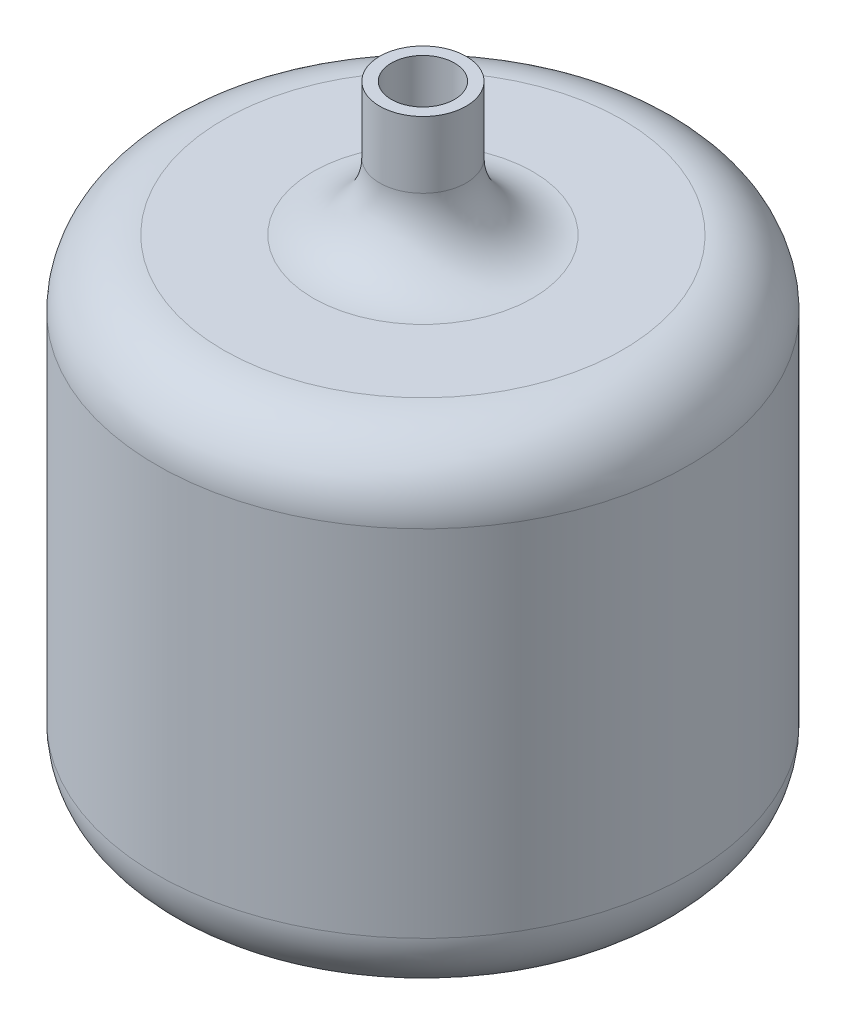
SolidWorks part; units mm, degrees
ref_plane "Plan de face" through (0, 0, 0) normal (1, 0, 0) x (0, 1, 0)
ref_plane "Plan de dessus" through (0, 0, 0) normal (0, 0, 1) x (0, 1, 0)
ref_plane "Plan de droite" through (0, 0, 0) normal (0, 1, 0) x (-1, 0, 0)
sketch "Esquisse1" plane through (0, 0, 0) normal (0, 0, 1) x (0, 1, 0)
  line L0 (0, 0) -> (64.4456, 0) construction
  line L1 (-31.0702, 40) -> (31.9298, 40)
  line L2 (-31.0702, 40) -> (-31.0702, 32.5)
  line L3 (-31.0702, 32.5) -> (31.9298, 32.5)
  line L4 (31.9298, 40) -> (31.9298, 32.5)
  line L5 (31.9298, 40) -> (41.9298, 40)
  line L6 (31.9298, 40) -> (31.9298, -40)
  line L7 (31.9298, -40) -> (41.9298, -40)
  line L8 (41.9298, 40) -> (41.9298, -40)
  line L9 (31.9298, -40) -> (-31.0702, -40)
  line L10 (31.9298, -40) -> (31.9298, -32.5)
  line L11 (31.9298, -32.5) -> (-31.0702, -32.5)
  line L12 (-31.0702, -40) -> (-31.0702, -32.5)
  dimension "D1" = 7.5
  dimension "D2" = 7.5
  dimension "D3" = 10
  dimension "D4" = 80
  dimension "D5" = 32.5
  dimension "D6" = 63
  dimension "D7" = 63
revolve "Révolution1" add sketch "Esquisse1" angle 360 about L0 region at (20, 36.9298, 0) region at (36.25, 0.4298, 0)
sketch "Esquisse2" plane through (0, 0, 0) normal (1, 0, 0) x (0, 1, 0)
  line L0 (-31.0702, 40) -> (-31.0702, -40) construction
  circle A0 centre (-21.0702, 0) radius 5.5
  circle A1 centre (-6.0702, 0) radius 5.5
  circle A2 centre (8.9298, 0) radius 5.5
  circle A3 centre (23.9298, 0) radius 5.5
  dimension "D1" = 11
  dimension "D3" = 11
  dimension "D5" = 11
  dimension "D7" = 11
  dimension "D2" = 10
  dimension "D4" = 15
  dimension "D6" = 15
  dimension "D8" = 15
extrude "Enlèv. mat.-Extru.1" cut sketch "Esquisse2" against normal blind 33
pattern_circular "Répétition circulaire1" count 15 every 24 about axis through (0, -31.0702, 0) along (0, -1, 0) of "Enlèv. mat.-Extru.1"
fillet "Congé1" radius 10 1 edges at (0, 41.9298, -40)
fillet "Congé2" radius 10 1 edges at (0, -31.0702, -40)
sketch "Esquisse3" plane through (0, 41.9298, 0) normal (0, 1, 0) x (-1, 0, 0)
  circle A0 centre (0, 0) radius 6.5
  circle A1 centre (0, 0) radius 4.75
  dimension "D1" = 13
  dimension "D2" = 9.5
extrude "Boss.-Extru.1" add sketch "Esquisse3" along normal blind 20
fillet "Congé3" radius 10 1 edges at (0, 41.9298, -6.5)
